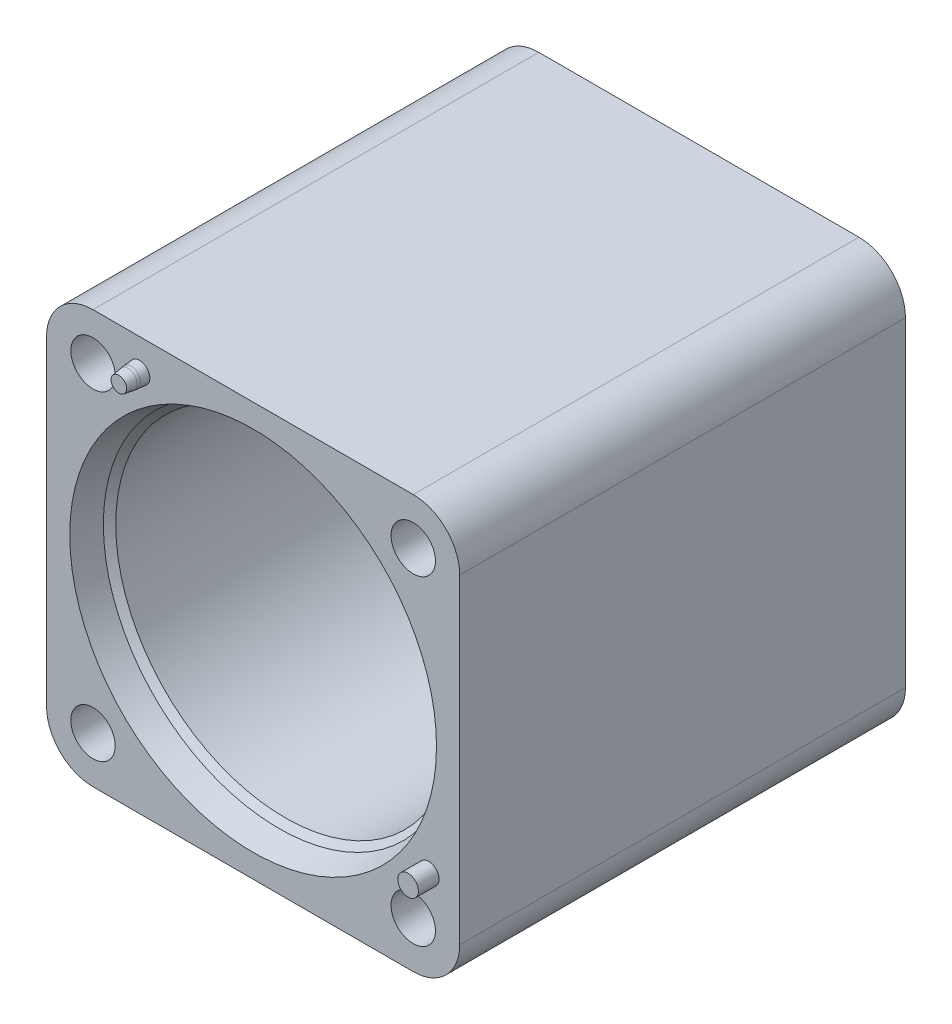
SolidWorks part; units mm, degrees
ref_plane "Front Plane" through (0, 0, 0) normal (0, 0, 1) x (1, 0, 0)
ref_plane "Top Plane" through (0, 0, 0) normal (0, 1, 0) x (1, 0, 0)
ref_plane "Right Plane" through (0, 0, 0) normal (1, 0, 0) x (0, 0, -1)
sketch "Sketch1" plane through (0, 0, 0) normal (0, 0, 1) x (1, 0, 0)
  line L1 (-15.5, -20) -> (15.5, -20)
  line L2 (-20, -15.5) -> (-20, 15.5)
  line L3 (-15.5, 20) -> (15.5, 20)
  line L4 (20, -15.5) -> (20, 15.5)
  line L5 (-20, -20) -> (20, 20) construction
  line L6 (-20, 20) -> (20, -20) construction
  circle A0 centre (0, 0) radius 17.75 construction
  circle A1 centre (0, 0) radius 16.4
  arc A2 (-15.5, -20) -> (-20, -15.5) centre (-15.5, -15.5) cw
  arc A3 (15.5, -20) -> (20, -15.5) centre (15.5, -15.5) ccw
  arc A4 (15.5, 20) -> (20, 15.5) centre (15.5, 15.5) cw
  arc A5 (-20, 15.5) -> (-15.5, 20) centre (-15.5, 15.5) cw
  circle A6 centre (-15.5, 15.5) radius 2.15
  circle A7 centre (15.5, 15.5) radius 2.15
  circle A8 centre (15.5, -15.5) radius 2.15
  circle A9 centre (-15.5, -15.5) radius 2.15
  point P0 (0, 0)
  point P31 (0, 0)
  dimension "D3" = 35.5
  dimension "D4" = 32.8
  dimension "D5" = 4.5
  dimension "D6" = 4.3
  dimension "D1" = 40
  dimension "D2" = 40
  dimension "D7" = 4
extrude "Boss-Extrude1" add sketch "Sketch1" along normal blind 43.15
sketch "Sketch5" plane through (0, 0, 0) normal (0, 1, 0) x (1, 0, 0)
  line L0 (0, -3.1) -> (16.4, -3.1) construction
  line L1 (16.4, -3.1) -> (17, -2.5)
  line L2 (17, -2.5) -> (17.75, 0)
  line L3 (20, 0) -> (15.5, 0) construction
  line L4 (16.4, -3.1) -> (16.4, 0)
  line L5 (16.4, 0) -> (-16.4, 0) construction
  line L6 (17.65, 0) -> (13.35, 0) construction
  line L7 (16.4, 0) -> (17.75, 0)
  dimension "D1" = 0.6
  dimension "D2" = 16.4
  dimension "D3" = 0.6
  dimension "D4" = 2.5
  dimension "D5" = 0.75
ref_axis "Axis1" through (0, 0, -2.15) along (0, 0, 1)
revolve "Cut-Revolve1" cut sketch "Sketch5" angle 360 about axis through (0, 0, -2.15) along (0, 0, 1)
ref_plane "Plane1" through (0, 0, 21.575) normal (0, 0, -1) x (-1, 0, 0)
mirror "Mirror1" about plane through (0, 0, 21.575) normal (0, 0, -1) of "Cut-Revolve1"
sketch "Sketch6" plane through (0, 0, 43.15) normal (0, 0, 1) x (1, 0, 0)
  line L0 (-20, 15.5) -> (-20, -15.5) construction
  line L1 (-15.5, -20) -> (15.5, -20) construction
  line L2 (-18.682, -18.682) -> (18.682, 18.682) construction
  circle A0 centre (-11, 17) radius 1
  arc A1 (-20, -15.5) -> (-15.5, -20) centre (-15.5, -15.5) ccw construction
  arc A2 (20, 15.5) -> (15.5, 20) centre (15.5, 15.5) ccw construction
  circle A3 centre (17, -11) radius 1
  dimension "D2" = 2
  dimension "D1" = 9
  dimension "D3" = 37
extrude "Boss-Extrude2" add sketch "Sketch6" along normal blind 2
sketch "Sketch7" plane through (0, 0, 45.15) normal (0, 0, 1) x (1, 0, 0)
  line L0 (-12, 17) -> (-10, 17) construction
  circle A0 centre (-11, 17) radius 1 construction
  circle A1 centre (-11, 17) radius 1 construction
ref_plane "Plane2" through (0, 17, 0) normal (0, 1, 0) x (1, 0, 0)
sketch "Sketch8" plane through (0, 17, 0) normal (0, 1, 0) x (1, 0, 0)
  line L1 (-12, -45.15) -> (-10, -45.15) construction
  line L2 (-10.0748, -43.9565) -> (-10, -43.15)
  line L3 (15.5, -43.15) -> (-15.5, -43.15) construction
  line L4 (-10, -43.15) -> (-10, -45.15)
  line L5 (-10, -45.15) -> (-10.25, -45.15)
  line L6 (-10.25, -45.15) -> (-10.1122, -44.2594)
  line L7 (-11, -45.15) -> (-11, -43.15) construction
  line L8 (-12, -43.15) -> (-10, -43.15) construction
  arc A1 (-10.1122, -44.2594) -> (-10.0748, -43.9565) centre (-15.0534, -43.4949) ccw
  dimension "D1" = 5
  dimension "D2" = 0.25
revolve "Cut-Revolve2" cut sketch "Sketch8" angle 360 about L7
